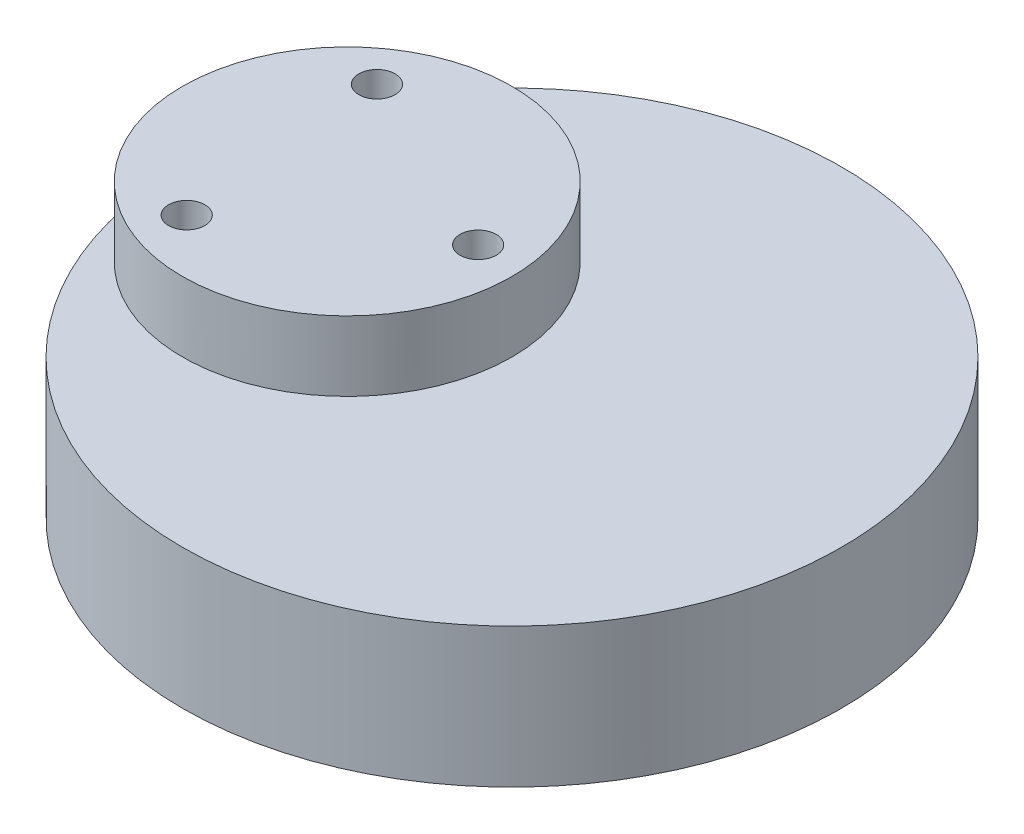
SolidWorks part; units mm, degrees
material "AISI 304"
ref_plane "Front Plane" through (0, 0, 0) normal (0, 0, 1) x (1, 0, 0)
ref_plane "Top Plane" through (0, 0, 0) normal (0, 1, 0) x (1, 0, 0)
ref_plane "Right Plane" through (0, 0, 0) normal (1, 0, 0) x (0, 0, -1)
sketch "Sketch2" plane through (0, 0, 0) normal (0, 1, 0) x (1, 0, 0)
  circle A0 centre (0, 0) radius 15
  circle A1 centre (15, 0) radius 30
  dimension "D1" = 30
  dimension "D2" = 60
  dimension "D3" = 15
extrude "Boss-Extrude1" add sketch "Sketch2" along normal blind 6.35 contours A0 region at (0, 0, 0)
extrude "Boss-Extrude2" add sketch "Sketch2<3>" against normal blind 12.7 contours A0 A1 | A0 region at (0, 0, 0) region at (20, 0, 0)
sketch "Sketch2<3>" plane through (0, 0, 0) normal (0, 1, 0) x (1, 0, 0) same geometry as "Sketch2"
hole_wizard "M4x0.7 Tapped Hole1" positions "Sketch3" profile "Sketch4" tap size "M4x0.7" standard "ANSI Metric"
sketch "Sketch3" plane through (0, 6.35, 0) normal (0, 1, 0) x (1, 0, 0)
  line L0 (-4.6488, -9.9694) -> (0, 0) construction
  line L1 (0, 0) -> (10.9581, 0.9587) construction
  line L3 (-6.3093, 9.0107) -> (0, 0) construction
  line L4 (0, -15) -> (0, 15) construction
  circle A0 centre (0, 0) radius 15 construction
  circle A1 centre (0, 0) radius 15 construction
  point P1 (-4.6488, -9.9694)
  point P5 (10.9581, 0.9587)
  point P7 (-6.3093, 9.0107)
  dimension "D1" = 120
  dimension "D2" = 120
  dimension "D3" = 11
  dimension "D4" = 25
sketch "Sketch4" plane through (-4.6488, 6.35, 9.9694) normal (1, 0, 0) x (0, 0, 1)
  line L0 (0, 0) -> (0, 11.0914)
  line L1 (0, 11.0914) -> (1.65, 10.1)
  line L2 (1.65, 10.1) -> (1.65, 0)
  line L5 (1.65, 0) -> (0, 0)
  line L10 (0, 11.0914) -> (-1.65, 10.1) construction
  line L11 (0, -6.35) -> (0, 107.95) construction
  dimension "Tap Drill Dia." = 3.3
  dimension "Tap Drill Depth" = 10.1
  dimension "Drill Angle" = 118
cosmetic thread "Hole Thread1"
cosmetic thread "Hole Thread2"
cosmetic thread "Hole Thread3"
hole_wizard "M4x0.7 Tapped Hole3" positions "Sketch5" profile "Sketch6" tap size "M4x0.7" standard "ANSI Metric"
sketch "Sketch5" plane through (0, -12.7, 0) normal (0, -1, 0) x (-1, 0, 0)
  line L0 (-15, -20) -> (-15, 0) construction
  line L1 (-15, 0) -> (2.3205, 10) construction
  line L3 (-32.3205, 10) -> (-15, 0) construction
  point P1 (-15, -20)
  point P5 (2.3205, 10)
  point P7 (-32.3205, 10)
  dimension "D1" = 120
  dimension "D2" = 120
  dimension "D3" = 20
sketch "Sketch6" plane through (15, -12.7, 20) normal (1, 0, 0) x (0, 0, -1)
  line L0 (0, 0) -> (0, 11.0914)
  line L1 (0, 11.0914) -> (1.65, 10.1)
  line L2 (1.65, 10.1) -> (1.65, 0)
  line L5 (1.65, 0) -> (0, 0)
  line L10 (0, 11.0914) -> (-1.65, 10.1) construction
  line L11 (0, -6.35) -> (0, 107.95) construction
  dimension "Tap Drill Dia." = 3.3
  dimension "Tap Drill Depth" = 10.1
  dimension "Drill Angle" = 118
cosmetic thread "Hole Thread4"
cosmetic thread "Hole Thread5"
cosmetic thread "Hole Thread6"
